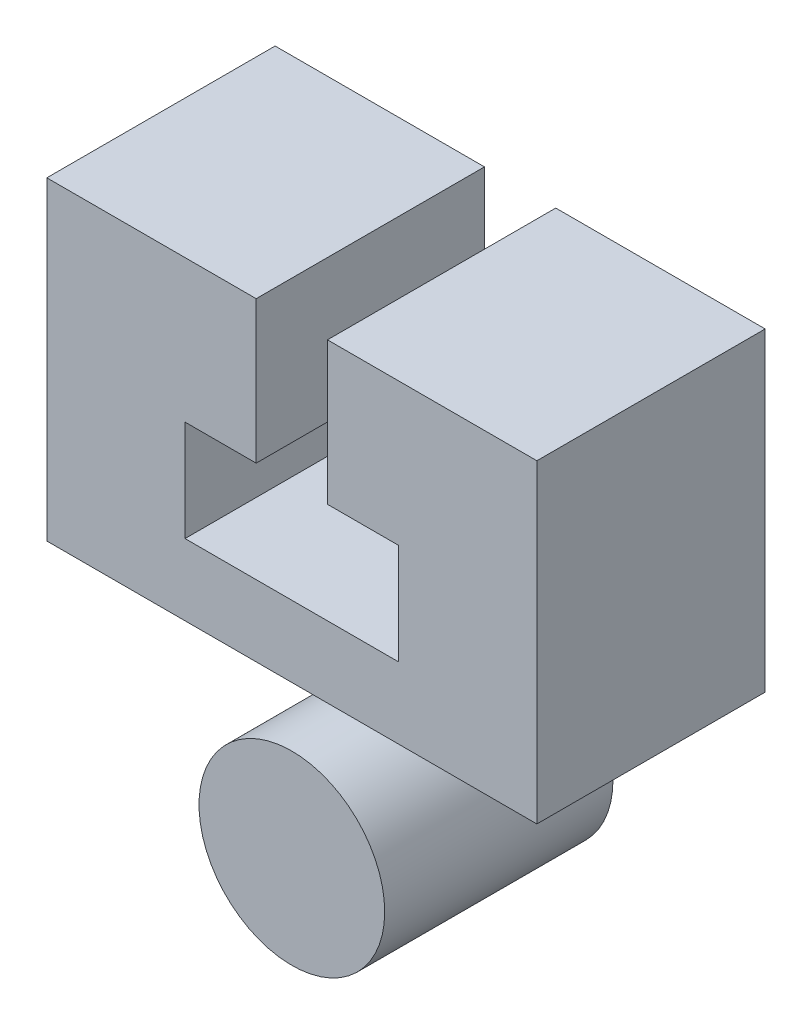
SolidWorks part; units mm, degrees
material "ASTM A36 Steel"
ref_plane "Front Plane" through (0, 0, 0) normal (0, 0, 1) x (1, 0, 0)
ref_plane "Top Plane" through (0, 0, 0) normal (0, 1, 0) x (1, 0, 0)
ref_plane "Right Plane" through (0, 0, 0) normal (1, 0, 0) x (0, 0, -1)
sketch "Sketch1" plane through (0, 0, 0) normal (0, 0, 1) x (1, 0, 0)
  circle A0 centre (0, 0) radius 15.494
  dimension "D1" = 30.988
extrude "Boss-Extrude1" add sketch "Sketch1" against normal blind 38.1
sketch "Sketch2" plane through (0, 0, -38.1) normal (0, 0, -1) x (-1, 0, 0)
  line L1 (-15.494, 0) -> (-15.494, 25.4)
  line L2 (-15.494, 25.4) -> (15.494, 25.4)
  line L3 (15.494, 25.4) -> (15.494, 0)
  circle A0 centre (0, 0) radius 15.494 construction
  arc A1 (15.494, 0) -> (-15.494, 0) centre (0, 0) ccw
  dimension "D1" = 25.4
  dimension "D2" = 30.988
extrude "Boss-Extrude2" add sketch "Sketch2" against normal blind 7.4168
sketch "Sketch3" plane through (0, 0, -38.1) normal (0, 0, -1) x (-1, 0, 0)
  line L0 (-15.494, 25.4) -> (-40.894, 25.4)
  line L1 (-40.894, 25.4) -> (-40.894, 77.9018)
  line L2 (-40.894, 77.9018) -> (40.894, 77.9018)
  line L3 (40.894, 77.9018) -> (40.894, 25.4)
  line L4 (40.894, 25.4) -> (15.494, 25.4)
  line L5 (15.494, 25.4) -> (-15.494, 25.4) construction
  line L6 (-15.494, 25.4) -> (15.494, 25.4)
  dimension "D1" = 25.4
  dimension "D2" = 25.4
  dimension "D3" = 52.5018
extrude "Boss-Extrude4" add sketch "Sketch3" against normal up to surface (38.1 mm away) up to face at (15.494, 0, 0)
sketch "Sketch4" plane through (0, 0, -38.1) normal (0, 0, -1) x (-1, 0, 0)
  line L0 (-5.9448, 77.9018) -> (-5.9448, 54.1274)
  line L1 (40.894, 77.9018) -> (-40.894, 77.9018) construction
  line L2 (-5.9448, 54.1274) -> (-17.8308, 54.1274)
  line L3 (-17.8308, 54.1274) -> (-17.8308, 37.2872)
  line L4 (-17.8308, 37.2872) -> (17.8308, 37.2872)
  line L5 (17.8308, 37.2872) -> (17.8308, 54.1274)
  line L6 (17.8308, 54.1274) -> (5.9555, 54.1274)
  line L7 (5.9555, 54.1274) -> (5.9555, 77.9018)
  line L8 (5.9555, 77.9018) -> (-5.9448, 77.9018)
  line L9 (-40.894, 25.4) -> (-15.494, 25.4) construction
  point P14 (0, 37.2872)
  dimension "D1" = 16.8402
  dimension "D2" = 11.8872
  dimension "D3" = 35.6616
  dimension "D4" = 11.886
  dimension "D5" = 11.8753
extrude "Cut-Extrude1" cut sketch "Sketch4" against normal through all
fillet "Fillet1" radius 5.08 1 edges at (0, 15.494, -30.6832)
equation "\"L\"= 1'Length"
equation "\"A\"= 1.22'A Diameter"
equation "\"B\"= 0.146'Thickness/Height"
equation "\"C\"= 0.468'Thickness/Height"
equation "\"D\"= 0.663'Thickness/Height"
equation "\"E\"= 0.936'Thickness/Height"
equation "\"D1@Sketch1\"=\"A\""
equation "\"D1@Boss-Extrude1\"=\"L\"+.5"
equation "\"D1@Sketch2\"=\"L\""
equation "\"D2@Sketch2\"=\"A\""
equation "\"D1@Boss-Extrude2\"=\"B\"*2"
equation "\"D1@Sketch3\"=\"L\""
equation "\"D2@Sketch3\"=\"L\""
equation "\"D3@Sketch3\"=\"C\"+\"D\"+\"E\""
equation "\"D1@Sketch4\"=\"D\""
equation "\"D2@Sketch4\"=\"C\""
equation "\"BC\"= \"C\" * 3'C Length"
equation "\"D3@Sketch4\"=\"BC\""
equation "\"D4@Sketch4\"=\"BC\"*.3333"
equation "\"D5@Sketch4\"=\"BC\"*.333"
